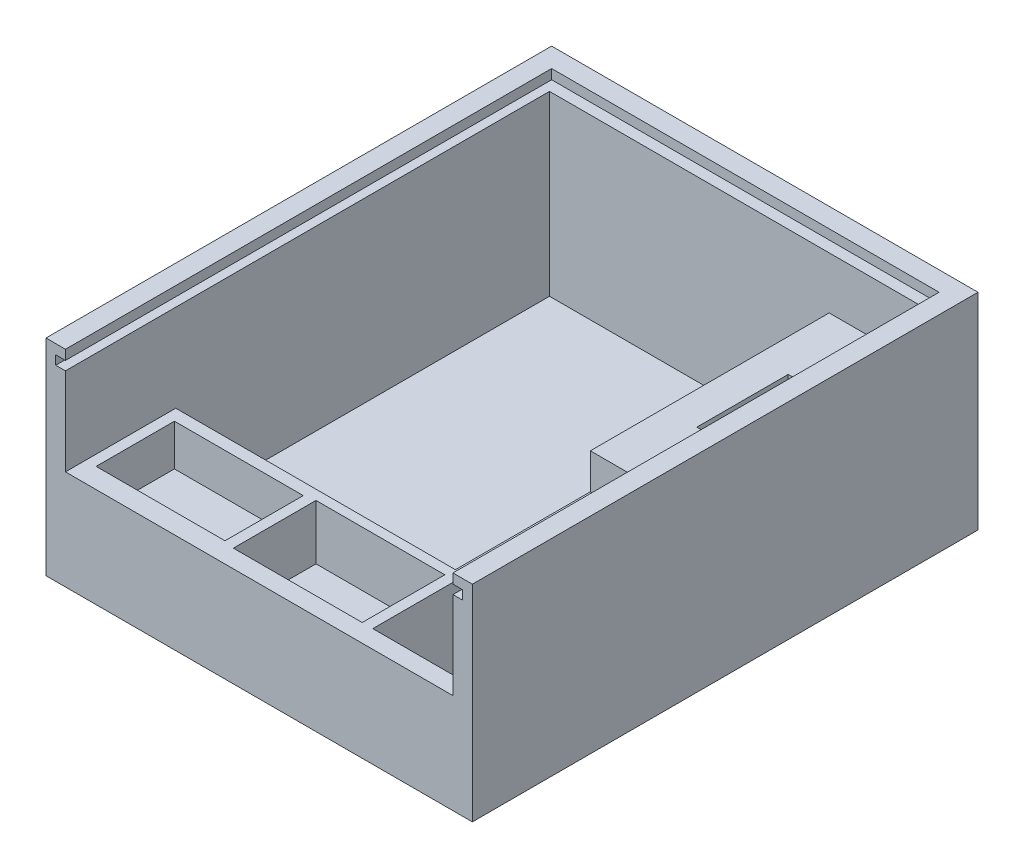
SolidWorks part; units mm, degrees
ref_plane "Front Plane" through (0, 0, 0) normal (0, 0, 1) x (1, 0, 0)
ref_plane "Top Plane" through (0, 0, 0) normal (0, 1, 0) x (1, 0, 0)
ref_plane "Right Plane" through (0, 0, 0) normal (1, 0, 0) x (0, 0, -1)
sketch "Sketch1" plane through (0, 0, 0) normal (0, 1, 0) x (1, 0, 0)
  line L0 (-39.85, -51) -> (-39.85, -48.5627)
  line L1 (-41.85, -51) -> (41.85, -51)
  line L2 (-41.85, -51) -> (-41.85, 51)
  line L3 (-41.85, 51) -> (41.85, 51)
  line L4 (41.85, -51) -> (41.85, 51)
  line L5 (-41.85, -51) -> (41.85, 51) construction
  line L6 (-41.85, 51) -> (41.85, -51) construction
  line L7 (-39.85, -48.5627) -> (-39.85, 48.5627)
  line L8 (-39.85, 48.5627) -> (39.85, 48.5627)
  line L9 (39.85, 48.5627) -> (39.85, -48.5627)
  line L10 (39.85, -48.5627) -> (39.85, -51)
  line L11 (-39.85, -48.5627) -> (39.85, -48.5627)
  line L12 (17.675, -0.5627) -> (17.675, -28.3127)
  line L29 (-37.675, -46.8627) -> (-11.175, -46.8627)
  line L30 (-37.675, -46.8627) -> (-37.675, -30.7627)
  line L31 (-37.675, -30.7627) -> (-11.175, -30.7627)
  line L32 (-11.175, -46.8627) -> (-11.175, -30.7627)
  line L33 (-37.675, -46.8627) -> (-11.175, -30.7627) construction
  line L34 (-37.675, -30.7627) -> (-11.175, -46.8627) construction
  line L35 (-9, -47.3127) -> (17.5, -47.3127)
  line L36 (-9, -47.3127) -> (-9, -30.3127)
  line L37 (-9, -30.3127) -> (17.5, -30.3127)
  line L38 (17.5, -47.3127) -> (17.5, -30.3127)
  line L39 (-9, -47.3127) -> (17.5, -30.3127) construction
  line L40 (-9, -30.3127) -> (17.5, -47.3127) construction
  line L41 (19.675, -47.3127) -> (37.675, -47.3127)
  line L42 (19.675, -47.3127) -> (19.675, -3.8127)
  line L43 (19.675, -3.8127) -> (37.675, -3.8127)
  line L44 (37.675, -47.3127) -> (37.675, -3.8127)
  line L45 (19.675, -47.3127) -> (37.675, -3.8127) construction
  line L46 (19.675, -3.8127) -> (37.675, -47.3127) construction
  line L47 (17.675, -0.5627) -> (39.85, -0.5627)
  line L48 (17.675, -0.5627) -> (17.675, 48.5627)
  line L49 (17.675, 48.5627) -> (39.85, 48.5627)
  line L50 (39.85, -0.5627) -> (39.85, 48.5627)
  line L51 (17.675, -0.5627) -> (39.85, 48.5627) construction
  line L52 (17.675, 48.5627) -> (39.85, -0.5627) construction
  line L53 (17.675, -28.3127) -> (-39.85, -28.3127)
  line L54 (-41.85, -51) -> (-43.85, -51)
  line L55 (24.4125, 14.6) -> (33.1125, 14.6)
  line L56 (24.4125, 14.6) -> (24.4125, 33.4)
  line L57 (24.4125, 33.4) -> (33.1125, 33.4)
  line L58 (33.1125, 14.6) -> (33.1125, 33.4)
  line L59 (24.4125, 14.6) -> (33.1125, 33.4) construction
  line L60 (24.4125, 33.4) -> (33.1125, 14.6) construction
  line L61 (-43.85, -51) -> (-43.85, 53)
  line L62 (-43.85, 53) -> (43.85, 53)
  line L63 (43.85, 53) -> (43.85, -51)
  line L64 (43.85, -51) -> (41.85, -51)
  point P0 (0, 0)
  point P12 (-24.425, -38.8127)
  point P17 (4.25, -38.8127)
  point P22 (28.675, -25.5627)
  point P27 (28.7625, 24)
  point P32 (28.7625, 24)
  dimension "D1" = 102
  dimension "D2" = 83.7
  dimension "D3" = 2
  dimension "D4" = 26.5
  dimension "D5" = 26.5
  dimension "D6" = 18
  dimension "D7" = 43.5
  dimension "D8" = 17
  dimension "D9" = 16.1
  dimension "D10" = 2
  dimension "D11" = 3.25
  dimension "D12" = 1.25
  dimension "D13" = 2
  dimension "D14" = 18.8
  dimension "D15" = 8.7
  dimension "D16" = 2.175
  dimension "D17" = 2.175
  dimension "D18" = 2.175
  dimension "D19" = 2
  dimension "D20" = 2
  dimension "D21" = 2
other "AlignGroup1"
other "AlignGroup2"
other "AlignGroup3"
extrude "Boss-Extrude1" add sketch "Sketch1" along normal blind 36.5 contours L9 L10 L1 L4 L3 L2 L0 L7 L8 region at (-40.85, 0, 49.6805)
extrude "Boss-Extrude2" add sketch "Sketch1<3>" along normal blind 40.35 contours L64 L63 L62 L61 L54 L2 L3 L4 region at (-42.85, 0, 49.6396)
sketch "Sketch1<3>" plane through (0, 0, 0) normal (0, 1, 0) x (1, 0, 0) same geometry as "Sketch1"
extrude "Boss-Extrude3" add sketch "Sketch1<4>" along normal blind 25.8 contours L48 L47 L9 L8 L58 L55 L56 L57 region at (28.7625, 0, 0.0237)
sketch "Sketch1<4>" plane through (0, 0, 0) normal (0, 1, 0) x (1, 0, 0) same geometry as "Sketch1"
extrude "Boss-Extrude4" add sketch "Sketch1<5>" along normal blind 20.8 contours L55 L58 L57 L56 region at (28.7625, 0, -24)
sketch "Sketch1<5>" plane through (0, 0, 0) normal (0, 1, 0) x (1, 0, 0) same geometry as "Sketch1"
extrude "Boss-Extrude5" add sketch "Sketch1<6>" along normal blind 7.2 separate body contours L35 L38 L37 L36 region at (4.25, 0, 38.8127)
sketch "Sketch1<6>" plane through (0, 0, 0) normal (0, 1, 0) x (1, 0, 0) same geometry as "Sketch1"
extrude "Boss-Extrude6" add sketch "Sketch1<7>" along normal blind 10 separate body contours L29 L32 L31 L30 region at (-24.425, 0, 38.8127)
sketch "Sketch1<7>" plane through (0, 0, 0) normal (0, 1, 0) x (1, 0, 0) same geometry as "Sketch1"
extrude "Boss-Extrude7" add sketch "Sketch1<8>" along normal blind 18.5 contours L12 L53 L7 L11 L9 L47 L44 L41 L42 L43 L38 L35 L36 L37 L32 L29 L30 L31 | L11 L0 L1 L10 region at (0, 0, 49.7814) region at (6.5942, 0, 29.6237)
sketch "Sketch1<8>" plane through (0, 0, 0) normal (0, 1, 0) x (1, 0, 0) same geometry as "Sketch1"
extrude "Boss-Extrude8" add sketch "Sketch1<9>" against normal blind 2 contours L11 L0 L1 L10 | L64 L63 L62 L61 L54 L2 L3 L4 | L9 L10 L1 L4 L3 L2 L0 L7 L8 | L12 L53 L7 L11 L9 L47 L44 L41 L42 L43 L38 L35 L36 L37 L32 L29 L30 L31 | L29 L32 L31 L30 | L35 L38 L37 L36 | L55 L58 L57 L56 | L48 L47 L9 L8 L58 L55 L56 L57 | L53 L12 L48 L8 L7 | L41 L44 L43 L42 region at (-40.85, 0, 49.6805) region at (0, 0, 49.7814) region at (6.5942, 0, 29.6237) region at (-42.85, 0, 49.6396) region at (-11.0875, 0, -10.125) region at (28.7625, 0, 0.0237) region at (-24.425, 0, 38.8127) region at (4.25, 0, 38.8127) region at (28.675, 0, 25.5627) region at (28.7625, 0, -24)
sketch "Sketch1<9>" plane through (0, 0, 0) normal (0, 1, 0) x (1, 0, 0) same geometry as "Sketch1"
sketch "Sketch2" plane through (0, 40.35, 0) normal (0, 1, 0) x (1, 0, 0)
  line L0 (-41.85, -51) -> (-41.85, 51)
  line L1 (-41.85, 51) -> (41.85, 51)
  line L2 (41.85, 51) -> (41.85, -51)
  line L3 (41.85, -51) -> (39.85, -51)
  line L4 (39.85, -51) -> (39.85, 49)
  line L5 (39.85, 49) -> (-39.85, 49)
  line L6 (-39.85, 49) -> (-39.85, -51)
  line L7 (-39.85, -51) -> (-41.85, -51)
  line L8 (-41.85, 51) -> (41.85, 51) construction
  dimension "D1" = 2
  dimension "D2" = 2
  dimension "D3" = 2
extrude "Boss-Extrude9" add sketch "Sketch2" against normal blind 2
